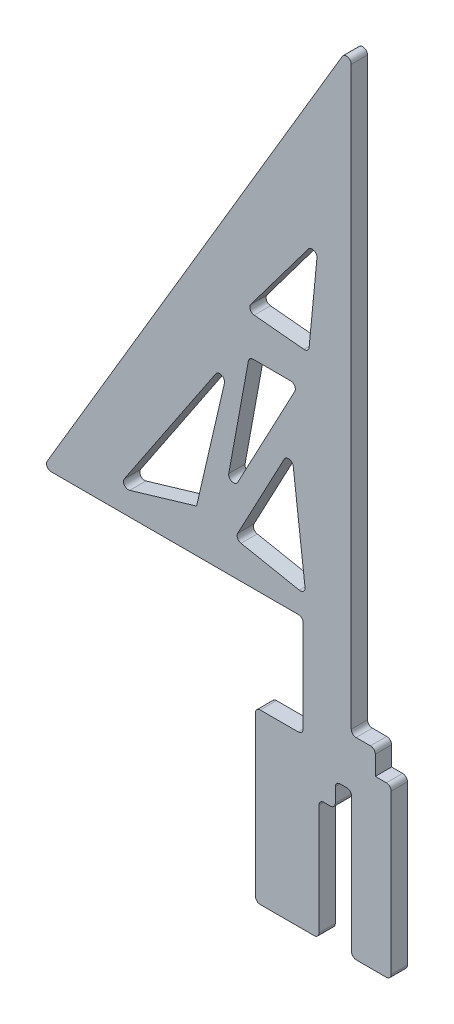
SolidWorks part; units mm, degrees
ref_plane "Front Plane" through (0, 0, 0) normal (0, 0, 1) x (1, 0, 0)
ref_plane "Top Plane" through (0, 0, 0) normal (0, 1, 0) x (1, 0, 0)
ref_plane "Right Plane" through (0, 0, 0) normal (1, 0, 0) x (0, 0, -1)
sketch "Sketch2" plane through (0, 0, 0) normal (0, 0, 1) x (1, 0, 0)
  line L0 (6.35, 101.6) -> (6.35, 186.3743)
  line L1 (-10.541, -22.225) -> (10.541, -22.225)
  line L2 (-10.541, -22.225) -> (-10.541, 22.225)
  line L3 (-10.541, 22.225) -> (10.541, 22.225)
  line L4 (10.541, -22.225) -> (10.541, 22.225)
  line L5 (-10.541, -22.225) -> (10.541, 22.225) construction
  line L6 (-10.541, 22.225) -> (10.541, -22.225) construction
  line L7 (-6.35, 0) -> (6.35, 0)
  line L8 (-6.35, 0) -> (-6.35, 101.6)
  line L9 (-6.35, 101.6) -> (6.35, 101.6)
  line L10 (6.35, 0) -> (6.35, 101.6)
  line L11 (6.35, 186.3743) -> (-74.9961, 49.0641)
  line L12 (-74.9961, 49.0641) -> (-6.35, 49.0641)
  point P0 (0, 0)
  point P10 (6.35, 186.3743)
  point P13 (-74.9961, 49.0641)
  dimension "D1" = 21.082
  dimension "D2" = 44.45
  dimension "D3" = 12.7
  dimension "D4" = 101.6
extrude "Boss-Extrude2" add sketch "Sketch2" along normal blind 4.2926 contours L3 L10 L9 L8 | L7 L10 L3 L8 | L10 L7 L8 L3 L2 L1 L4 region at (0, 61.9125, 0) region at (0, 11.1125, 0) region at (0, -4.7899, 0)
extrude "Boss-Extrude3" add sketch "Sketch2<3>" along normal blind 4.2926 contours L11 L12 L8 L9 L0 region at (-23.5827, 97.4802, 0)
sketch "Sketch2<3>" plane through (0, 0, 0) normal (0, 0, 1) x (1, 0, 0) same geometry as "Sketch2"
sketch "Sketch4" plane through (0, 0, 0) normal (0, 0, -1) x (-1, 0, 0)
  line L0 (2.2618, 137.4993) -> (4.8822, 110.2623)
  line L1 (4.8822, 110.2623) -> (21.502, 111.8613)
  line L2 (21.502, 111.8613) -> (2.2618, 137.4993)
  line L6 (25.5345, 98.9322) -> (34.4492, 60.4162)
  line L7 (34.4492, 60.4162) -> (55.4732, 54.1884)
  line L8 (55.4732, 54.1884) -> (25.5345, 98.9322)
  line L9 (9.4299, 86.2701) -> (5.634, 54.4214)
  line L10 (5.634, 54.4214) -> (24.4105, 58.1071)
  line L11 (24.4105, 58.1071) -> (9.4299, 86.2701)
  line L12 (7.5561, 101.4337) -> (27.4321, 64.0675)
  line L13 (27.4321, 64.0675) -> (20.5991, 101.4337)
  line L14 (20.5991, 101.4337) -> (7.5561, 101.4337)
extrude "Cut-Extrude1" cut sketch "Sketch4" against normal blind 4.2926
fillet "Fillet3" radius 1.27 14 edges at (6.35, 186.3743, 2.1463) (-74.9961, 49.0641, 2.1463) (-6.35, 49.0641, 2.1463) (-20.5991, 101.4337, 2.1463) (-7.5561, 101.4337, 2.1463) (-21.502, 111.8613, 2.1463) (-4.8822, 110.2623, 2.1463) (-2.2618, 137.4993, 2.1463) (-25.5345, 98.9322, 2.1463) (-55.4732, 54.1884, 2.1463) (-27.4321, 64.0675, 2.1463) (-9.4299, 86.2701, 2.1463) (-5.634, 54.4214, 2.1463) (-24.4105, 58.1071, 2.1463)
sketch "Sketch5" plane through (0, 0, 0) normal (0, 0, -1) x (-1, 0, 0)
  line L5 (10.541, -22.225) -> (-10.541, -22.225) construction
  line L6 (-2.1463, -22.225) -> (2.1463, -22.225)
  line L7 (-2.1463, -22.225) -> (-2.1463, 9.525)
  line L8 (-2.1463, 9.525) -> (2.1463, 9.525)
  line L9 (2.1463, -22.225) -> (2.1463, 9.525)
  line L10 (-2.1463, -22.225) -> (2.1463, 9.525) construction
  line L11 (-2.1463, 9.525) -> (2.1463, -22.225) construction
  point P0 (0, -6.35)
  dimension "D1" = 31.75
  dimension "D2" = 4.2926
extrude "Cut-Extrude2" cut sketch "Sketch5" against normal blind 4.2926
sketch "Sketch6" plane through (0, 0, 0) normal (0, 0, -1) x (-1, 0, 0)
  line L0 (-6.35, 22.225) -> (-10.541, 22.225) construction
  line L1 (-2.1463, -22.225) -> (-6.4389, -22.225)
  line L2 (-2.1463, -22.225) -> (-2.1463, 15.875)
  line L3 (-2.1463, 15.875) -> (-6.4389, 15.875)
  line L4 (-6.4389, -22.225) -> (-6.4389, 15.875)
  line L5 (-2.1463, -22.225) -> (-6.4389, 15.875) construction
  line L6 (-2.1463, 15.875) -> (-6.4389, -22.225) construction
  line L7 (-2.1463, -22.225) -> (-10.541, -22.225) construction
  line L8 (-2.1463, 9.525) -> (-2.1463, -22.225) construction
  point P0 (-4.2926, -3.175)
  dimension "D1" = 4.2926
  dimension "D2" = 6.35
extrude "Cut-Extrude3" cut sketch "Sketch6" against normal blind 4.2926
sketch "Sketch9" plane through (10.541, 0, 0) normal (1, 0, 0) x (0, 0, -1)
  line L1 (-4.2926, -22.225) -> (0, -22.225)
  line L2 (-4.2926, -22.225) -> (-4.2926, 22.225)
  line L3 (-4.2926, 22.225) -> (0, 22.225)
  line L4 (0, -22.225) -> (0, 22.225)
extrude "Boss-Extrude4" add sketch "Sketch9" along normal blind 6.35
sketch "Sketch10" plane through (6.35, 0, 0) normal (1, 0, 0) x (0, 0, -1)
  line L0 (0, 22.225) -> (0, 181.7389) construction
  line L1 (-4.2926, 22.225) -> (0, 22.225)
  line L2 (-4.2926, 22.225) -> (-4.2926, 28.575)
  line L3 (-4.2926, 28.575) -> (0, 28.575)
  line L4 (0, 22.225) -> (0, 28.575)
  dimension "D1" = 6.35
extrude "Boss-Extrude5" add sketch "Sketch10" along normal blind 6.35
sketch "Sketch12" plane through (-10.541, 0, 0) normal (-1, 0, 0) x (0, 0, 1)
  line L1 (0, -22.225) -> (4.2926, -22.225)
  line L2 (0, -22.225) -> (0, 22.225)
  line L3 (0, 22.225) -> (4.2926, 22.225)
  line L4 (4.2926, -22.225) -> (4.2926, 22.225)
extrude "Boss-Extrude6" add sketch "Sketch12" along normal blind 8.382
fillet "Fillet4" radius 1.27 13 edges at (6.4389, 15.875, 2.1463) (2.1463, 15.875, 2.1463) (-2.1463, 9.525, 2.1463) (2.1463, 9.525, 2.1463) (-6.35, 22.225, 2.1463) (-2.1463, -22.225, 2.1463) (6.4389, -22.225, 2.1463) (16.891, -22.225, 2.1463) (16.891, 22.225, 2.1463) (6.35, 28.575, 2.1463) (12.7, 28.575, 2.1463) (-18.923, -22.225, 2.1463) (-18.923, 22.225, 2.1463)
